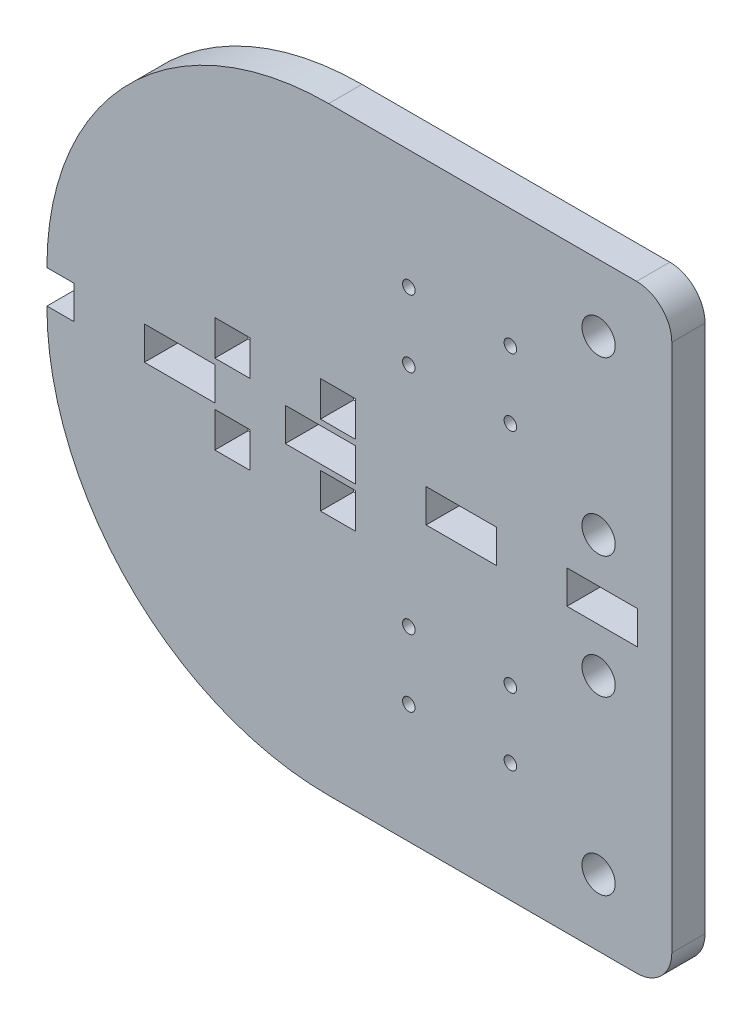
SolidWorks part; units mm, degrees
ref_plane "Front Plane" through (0, 0, 0) normal (0, 0, 1) x (1, 0, 0)
ref_plane "Top Plane" through (0, 0, 0) normal (0, 1, 0) x (1, 0, 0)
ref_plane "Right Plane" through (0, 0, 0) normal (1, 0, 0) x (0, 0, -1)
sketch "Sketch1" plane through (0, 0, 0) normal (0, 0, 1) x (-1, 0, 0)
  line L0 (5.4449, 19.1182) -> (-12.8627, 19.1182) construction
  line L1 (-15.4204, 35.8131) -> (8.0026, 35.8131) construction
  line L2 (-15.4204, 35.8131) -> (-15.4204, 14.5439) construction
  line L3 (-15.4204, 14.5439) -> (8.0026, 14.5439) construction
  line L4 (8.0026, 35.8131) -> (8.0026, 14.5439) construction
  line L5 (5.4449, 19.1182) -> (5.4449, 31.2335) construction
  line L6 (5.4449, 31.2335) -> (-12.8627, 31.2335) construction
  line L7 (-12.8627, 31.2335) -> (-12.8627, 19.1182) construction
  line L8 (-15.4204, 14.5439) -> (-15.4204, -17.2061) construction
  line L9 (-35.7704, 4.6785) -> (-35.7704, 45.6785) construction
  line L10 (-35.7704, 45.6785) -> (-21.7704, 45.6785) construction
  line L11 (-21.7704, 45.6785) -> (-21.7704, 4.6785) construction
  line L12 (-21.7704, 4.6785) -> (-35.7704, 4.6785) construction
  line L13 (-1015.4204, -1.3311) -> (48984.5796, -1.3311) construction
  line L14 (-35.7704, 1.6661) -> (-23.0704, 1.6661)
  line L15 (-21.7704, -7.3406) -> (-35.7704, -7.3406) construction
  line L16 (-21.7704, -48.3406) -> (-21.7704, -7.3406) construction
  line L17 (-35.7704, -48.3406) -> (-21.7704, -48.3406) construction
  line L18 (-35.7704, -7.3406) -> (-35.7704, -48.3406) construction
  line L19 (-12.8627, -33.8956) -> (-12.8627, -21.7803) construction
  line L20 (5.4449, -33.8956) -> (-12.8627, -33.8956) construction
  line L21 (5.4449, -21.7803) -> (5.4449, -33.8956) construction
  line L22 (8.0026, -38.4752) -> (8.0026, -17.2061) construction
  line L23 (-15.4204, -17.2061) -> (8.0026, -17.2061) construction
  line L24 (-15.4204, -38.4752) -> (-15.4204, -17.2061) construction
  line L25 (-15.4204, -38.4752) -> (8.0026, -38.4752) construction
  line L26 (5.4449, -21.7803) -> (-12.8627, -21.7803) construction
  line L27 (-15.4204, -27.8406) -> (-21.7704, -27.8406)
  line L28 (-15.4204, -1.3311) -> (-15.4204, 8.6689) construction
  line L29 (-10.3704, 1.6661) -> (2.3296, 1.6661)
  line L30 (70.7026, -4.3283) -> (70.7026, -4.5542)
  line L31 (15.0296, 1.6661) -> (27.7296, 1.6661)
  line L32 (-964.4397, 2.6689) -> (49035.5603, 2.6689) construction
  line L33 (-964.4397, -5.3311) -> (49035.5603, -5.3311) construction
  line L34 (40.4296, 1.6661) -> (53.1296, 1.6661)
  line L35 (65.8296, 1.6661) -> (70.7026, 1.6661)
  line L36 (15.0296, 2.6689) -> (15.0296, 9.0189)
  line L37 (15.0296, 9.0189) -> (21.3796, 9.0189)
  line L38 (15.0296, 2.6689) -> (21.3796, 2.6689)
  line L39 (19.9026, 52.6921) -> (-35.6234, 52.6921)
  line L40 (40.4296, -5.3311) -> (40.4296, -11.6811)
  line L41 (34.0796, -5.3311) -> (40.4296, -5.3311)
  line L42 (34.0796, -11.6811) -> (40.4296, -11.6811)
  line L43 (34.0796, -5.3311) -> (34.0796, -11.6811)
  line L44 (-35.7704, -4.3283) -> (-35.7704, 1.6661)
  line L45 (21.3796, 2.6689) -> (21.3796, 9.0189)
  line L46 (-23.0704, 1.6661) -> (-23.0704, -4.3283)
  line L47 (21.3796, -5.3311) -> (21.3796, -11.6811)
  line L48 (-10.3704, -4.3283) -> (-10.3704, 1.6661)
  line L49 (34.0796, 2.6689) -> (34.0796, 9.0189)
  line L50 (34.0796, 9.0189) -> (40.4296, 9.0189)
  line L51 (19.9026, -55.3542) -> (-35.6234, -55.3542)
  line L52 (-41.9734, 46.3421) -> (-41.9734, -49.0042)
  line L53 (34.0796, 2.6689) -> (40.4296, 2.6689)
  line L54 (2.3296, 1.6661) -> (2.3296, -4.3283)
  line L55 (15.0296, -5.3311) -> (21.3796, -5.3311)
  line L56 (15.0296, -4.3283) -> (15.0296, 1.6661)
  line L57 (40.4296, 2.6689) -> (40.4296, 9.0189)
  line L58 (27.7296, 1.6661) -> (27.7296, -4.3283)
  line L59 (15.0296, -11.6811) -> (21.3796, -11.6811)
  line L60 (40.4296, -4.3283) -> (40.4296, 1.6661)
  line L61 (70.7026, 1.6661) -> (70.7026, 1.8921)
  line L62 (53.1296, 1.6661) -> (53.1296, -4.3283)
  line L63 (15.0296, -5.3311) -> (15.0296, -11.6811)
  line L64 (65.8296, -4.3283) -> (65.8296, 1.6661)
  line L65 (-15.4204, 25.1785) -> (-21.7704, 25.1785)
  line L66 (65.8296, -4.3283) -> (70.7026, -4.3283)
  line L67 (40.4296, -4.3283) -> (53.1296, -4.3283)
  line L68 (15.0296, -4.3283) -> (27.7296, -4.3283)
  line L69 (-10.3704, -4.3283) -> (2.3296, -4.3283)
  line L70 (-35.7704, -4.3283) -> (-23.0704, -4.3283)
  arc A0 (-35.6234, 52.6921) -> (-41.9734, 46.3421) centre (-35.6234, 46.3421) ccw
  arc A1 (70.7026, 1.8921) -> (19.9026, 52.6921) centre (19.9026, 1.8921) ccw
  circle A2 centre (-12.8627, 31.2335) radius 1.1321
  circle A3 centre (5.4449, 31.2335) radius 1.1321
  circle A4 centre (-28.7704, -43.3406) radius 3
  circle A5 centre (-28.7704, -12.3406) radius 3
  circle A6 centre (-12.8627, -21.7803) radius 1.1321
  circle A7 centre (5.4449, -21.7803) radius 1.1321
  circle A8 centre (5.4449, 19.1182) radius 1.1321
  circle A9 centre (-12.8627, 19.1182) radius 1.1321
  circle A10 centre (5.4449, -33.8956) radius 1.1321
  circle A11 centre (-12.8627, -33.8956) radius 1.1321
  circle A12 centre (-28.7704, 9.6785) radius 3
  arc A13 (70.7026, -4.5542) -> (19.9026, -55.3542) centre (19.9026, -4.5542) cw
  circle A14 centre (-28.7704, 40.6785) radius 3
  arc A19 (-35.6234, -55.3542) -> (-41.9734, -49.0042) centre (-35.6234, -49.0042) cw
  point P42 (-15.4204, -1.3311)
  point P78 (-41.9734, 45.6785)
  dimension "D11" = 6.35
  dimension "D13" = 50.8
  dimension "D5" = 31.75
  dimension "D12" = 4
extrude "Boss-Extrude1" add sketch "Sketch1" along normal blind 5.9944 contours A19 L51 L57 L52 A10 A6 A4 A5 A7 A11 region at (-10.001, 1.3311, 0)
